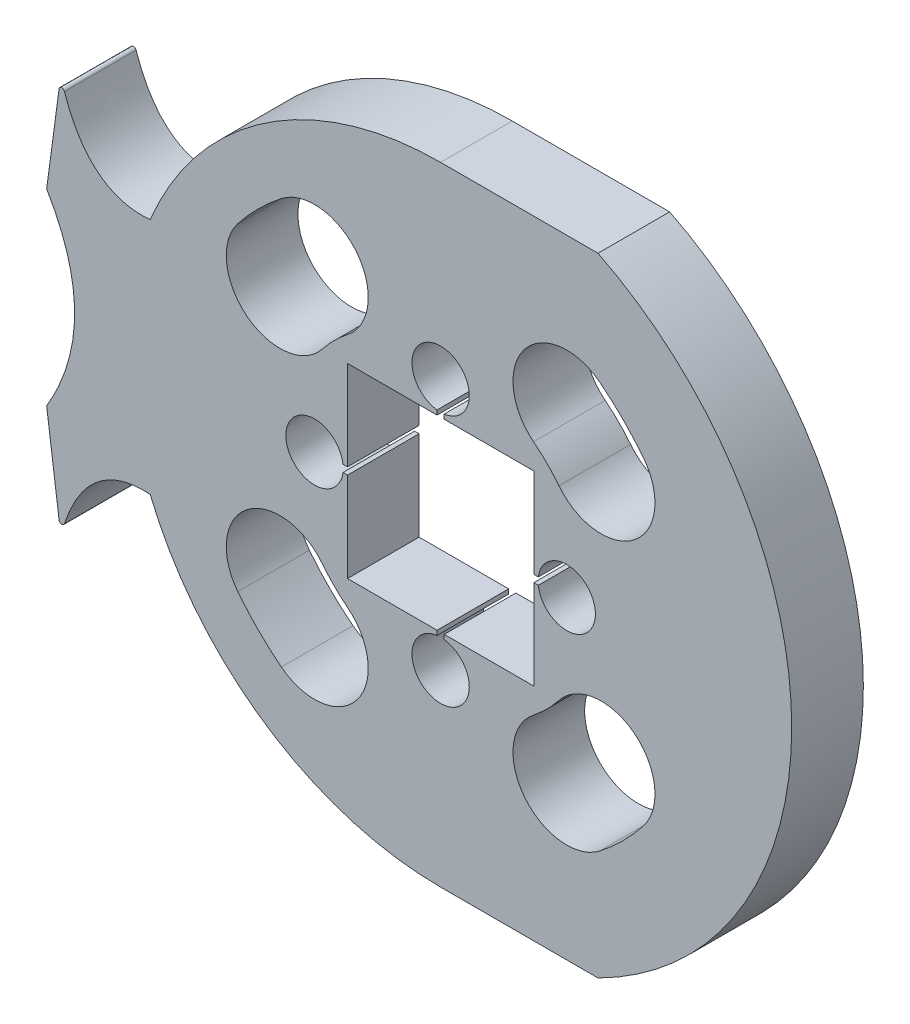
SolidWorks part; units mm, degrees
material "AISI 1020 Steel, Cold Rolled"
ref_plane "Front Plane" through (0, 0, 0) normal (0, 0, 1) x (1, 0, 0)
ref_plane "Top Plane" through (0, 0, 0) normal (0, 1, 0) x (1, 0, 0)
ref_plane "Right Plane" through (0, 0, 0) normal (1, 0, 0) x (0, 0, -1)
other "Center of Mass"
sketch "Sketch1" plane through (0, 0, 0) normal (0, 0, 1) x (1, 0, 0)
  line L0 (-11.176, 0) -> (0, 0) construction
  line L1 (-8.255, 8.255) -> (8.255, 8.255)
  line L2 (-8.255, 8.255) -> (-8.255, -8.255)
  line L3 (-8.255, -8.255) -> (8.255, -8.255)
  line L4 (8.255, 8.255) -> (8.255, -8.255)
  line L5 (0, 0) -> (0, 11.176) construction
  line L6 (11.176, 0) -> (0, 0) construction
  line L7 (0, 0) -> (0, -11.176) construction
  line L9 (-8.6559, 0.3175) -> (8.6559, 0.3175)
  line L10 (-8.6559, 0.3175) -> (-8.6559, -0.3175)
  line L11 (-8.6559, -0.3175) -> (8.6559, -0.3175)
  line L12 (8.6559, 0.3175) -> (8.6559, -0.3175)
  line L13 (-0.3175, 8.6559) -> (0.3175, 8.6559)
  line L14 (-0.3175, 8.6559) -> (-0.3175, -8.6559)
  line L15 (-0.3175, -8.6559) -> (0.3175, -8.6559)
  line L16 (0.3175, 8.6559) -> (0.3175, -8.6559)
  line L17 (0, 27.813) -> (13.9492, 27.813)
  line L18 (0, -27.813) -> (13.9492, -27.813)
  line L19 (-33.8048, 16.6086) -> (-34.9172, 8.3198)
  line L20 (-34.9172, -8.3198) -> (-33.8048, -16.6086)
  arc A0 (8.2349, -10.4885) -> (10.4885, -8.2349) centre (0, 0) ccw
  circle A1 centre (0, 11.176) radius 2.54
  circle A2 centre (0, -11.176) radius 2.54
  circle A3 centre (11.176, 0) radius 2.54
  circle A4 centre (-11.176, 0) radius 2.54
  arc A5 (14.1171, -17.9802) -> (17.9802, -14.1171) centre (0, 0) ccw
  arc A7 (-17.9802, 14.1171) -> (-10.4885, 8.2349) centre (-14.2343, 11.176) ccw
  arc A8 (-10.4885, -8.2349) -> (-17.9802, -14.1171) centre (-14.2343, -11.176) ccw
  arc A10 (-8.2349, 10.4885) -> (-14.1171, 17.9802) centre (-11.176, 14.2343) ccw
  arc A11 (17.9802, -14.1171) -> (10.4885, -8.2349) centre (14.2343, -11.176) ccw
  arc A13 (-14.1171, -17.9802) -> (-8.2349, -10.4885) centre (-11.176, -14.2343) ccw
  arc A14 (8.2349, -10.4885) -> (14.1171, -17.9802) centre (11.176, -14.2343) ccw
  arc A15 (-10.4885, -8.2349) -> (-8.2349, -10.4885) centre (0, 0) ccw
  arc A16 (-17.9802, -14.1171) -> (-14.1171, -17.9802) centre (0, 0) ccw
  arc A19 (-8.2349, 10.4885) -> (-10.4885, 8.2349) centre (0, 0) ccw
  arc A20 (-14.1171, 17.9802) -> (-17.9802, 14.1171) centre (0, 0) ccw
  arc A23 (10.4885, 8.2349) -> (17.9802, 14.1171) centre (14.2343, 11.176) ccw [skipped]
  arc A24 (14.1171, 17.9802) -> (8.2349, 10.4885) centre (11.176, 14.2343) ccw [skipped]
  arc A25 (-8.2349, 10.4885) -> (-14.1171, 17.9802) centre (-11.176, 14.2343) ccw
  arc A26 (-17.9802, 14.1171) -> (-10.4885, 8.2349) centre (-14.2343, 11.176) ccw
  arc A27 (-14.1171, 17.9802) -> (-17.9802, 14.1171) centre (0, 0) ccw
  arc A28 (10.4885, 8.2349) -> (17.9802, 14.1171) centre (14.2343, 11.176) ccw
  arc A29 (14.1171, 17.9802) -> (8.2349, 10.4885) centre (11.176, 14.2343) ccw
  arc A30 (17.9802, 14.1171) -> (14.1171, 17.9802) centre (0, 0) ccw
  arc A31 (8.2349, -10.4885) -> (14.1171, -17.9802) centre (11.176, -14.2343) ccw
  arc A32 (17.9802, -14.1171) -> (10.4885, -8.2349) centre (14.2343, -11.176) ccw
  arc A33 (14.1171, -17.9802) -> (17.9802, -14.1171) centre (0, 0) ccw
  arc A34 (-8.2349, 10.4885) -> (-10.4885, 8.2349) centre (0, 0) ccw
  arc A35 (10.4885, 8.2349) -> (8.2349, 10.4885) centre (0, 0) ccw
  arc A36 (8.2349, -10.4885) -> (10.4885, -8.2349) centre (0, 0) ccw
  arc A37 (-25.7359, -10.5464) -> (0, -27.813) centre (0, 0) ccw
  arc A39 (-33.3353, 16.5776) -> (-33.8048, 16.6086) centre (-33.5763, 16.4976) ccw
  arc A40 (-33.3353, -16.5776) -> (-33.8048, -16.6086) centre (-33.5763, -16.4976) cw
  arc A41 (13.9492, -27.813) -> (13.9492, 27.813) centre (0, 0) ccw
  arc A42 (0, 27.813) -> (-25.7359, 10.5464) centre (0, 0) ccw
  spline S0 degree 3 poles (-33.3353, 16.5776) (-31.8977, 12.2441) (-29.218, 10.1877) (-25.7359, 10.5464) knots 0.081541 0.081541 0.081541 0.081541 1 1 1 1
  spline S1 degree 3 poles (-33.3353, -16.5776) (-31.8977, -12.2441) (-29.2304, -10.2896) (-25.7359, -10.5464) knots 0.081541 0.081541 0.081541 0.081541 1 1 1 1
  spline S2 degree 2 poles (-34.9172, 8.3198) (-29.9564, 0) (-34.9172, -8.3198) knots 0 0 0 1 1 1
  point P7 (8.255, 0)
  point P8 (0, 8.255)
  point P54 (0, 0)
  point P70 (0, 0)
  point P77 (0, 0)
  point P78 (-32.4368, 0)
  point P80 (0, 0)
  point P82 (0, 0)
  dimension "D2" = 26.67
  dimension "D4" = 5.08
  dimension "D6" = 45.72
  dimension "D7" = 4
  dimension "D10" = 55.626
  dimension "D12" = 0.254
  dimension "D14" = 62.23
  dimension "D1" = 16.51
  dimension "D3" = 11.176
  dimension "D5" = 0.635
  dimension "D9" = 4
  dimension "D8" = 4
extrude "Boss-Extrude1" add sketch "Sketch1" along normal blind 6.35 contours A0 A4 L9 L2 L1 L14 A1 L16 L4 A3 L11 L3 A2 region at (6.9746, 26.9496, 0)
